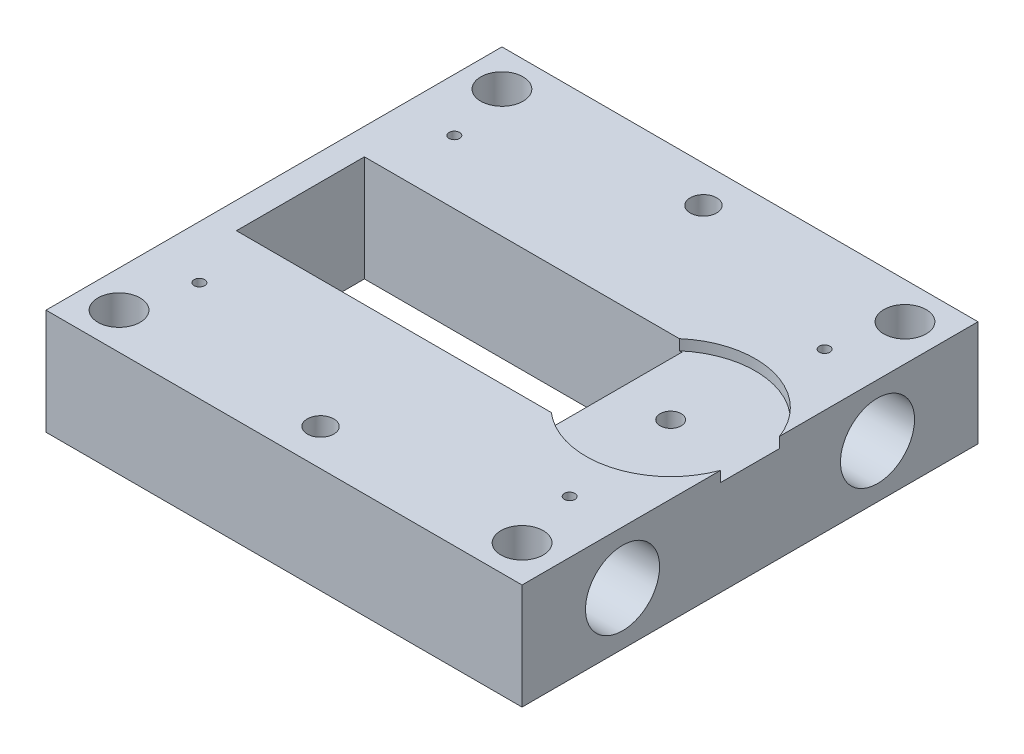
SolidWorks part; units mm, degrees
ref_plane "Front Plane" through (0, 0, 0) normal (0, 0, 1) x (1, 0, 0)
ref_plane "Top Plane" through (0, 0, 0) normal (0, 1, 0) x (1, 0, 0)
ref_plane "Right Plane" through (0, 0, 0) normal (1, 0, 0) x (0, 0, -1)
sketch "Sketch2" plane through (0, 0, 0) normal (1, 0, 0) x (0, 0, -1)
  line L0 (-24.1, 0) -> (24.1, 0) construction
  line L5 (-38.1, 0) -> (38.1, 0) construction
  line L6 (-43.1, -10) -> (43.1, -10)
  line L7 (-43.1, -10) -> (-43.1, 10)
  line L8 (-43.1, 10) -> (43.1, 10)
  line L9 (43.1, -10) -> (43.1, 10)
  line L10 (-43.1, -10) -> (43.1, 10) construction
  line L11 (-43.1, 10) -> (43.1, -10) construction
  circle A0 centre (-24.1, 0) radius 7
  circle A1 centre (24.1, 0) radius 7
  point P4 (0, 0)
  point P6 (0, 0)
  point P12 (-24.1, 7)
  point P14 (-31.1, 0)
  dimension "D1" = 14
  dimension "D2" = 3
  dimension "D3" = 76.2
  dimension "D4" = 5
  dimension "D5" = 7
extrude "Boss-Extrude1" add sketch "Sketch2" along normal mid plane 90
sketch "Sketch3" plane through (0, -10, 0) normal (0, -1, 0) x (1, 0, 0)
  line L1 (-38.1, -36.195) -> (38.1, -36.195) construction
  line L2 (-38.1, -36.195) -> (-38.1, 36.195) construction
  line L3 (-38.1, 36.195) -> (38.1, 36.195) construction
  line L4 (38.1, -36.195) -> (38.1, 36.195) construction
  line L5 (-38.1, -36.195) -> (38.1, 36.195) construction
  line L6 (-38.1, 36.195) -> (38.1, -36.195) construction
  circle A0 centre (-38.1, 36.195) radius 1.375
  circle A1 centre (38.1, 36.195) radius 1.375
  circle A2 centre (38.1, -36.195) radius 1.375
  circle A3 centre (-38.1, -36.195) radius 1.375
  point P0 (0, 0)
  dimension "D3" = 2.75
  dimension "D1" = 72.39
  dimension "D2" = 76.2
extrude "Cut-Extrude1" cut sketch "Sketch3" against normal through all
sketch "Sketch4" plane through (0, 10, 0) normal (0, 1, 0) x (1, 0, 0)
  circle A0 centre (-38.1, -36.195) radius 4
  circle A1 centre (-38.1, 36.195) radius 4
  circle A2 centre (38.1, 36.195) radius 4
  circle A3 centre (38.1, -36.195) radius 4
  dimension "D1" = 8
extrude "Cut-Extrude2" cut sketch "Sketch4" against normal offset from surface (17 mm away) 3 up to face at (-38.1, -10, -37.57)
sketch "Sketch5" plane through (0, 0, 0) normal (1, 0, 0) x (0, 0, -1)
  circle A0 centre (24.1, 0) radius 7 construction
  circle A1 centre (-24.1, 0) radius 7 construction
  circle A2 centre (24.1, 0) radius 7
  circle A3 centre (-24.1, 0) radius 7
  circle A4 centre (-24.1, 0) radius 5
  circle A5 centre (24.1, 0) radius 5
  dimension "D1" = 10
extrude "Boss-Extrude2" add sketch "Sketch5" along normal mid plane 42
sketch "Sketch6" plane through (0, 10, 0) normal (0, 1, 0) x (1, 0, 0)
  line L0 (45, 43.1) -> (45, -43.1) construction
  circle A0 centre (30, 0) radius 2
  circle A1 centre (0, -36.195) radius 2.5
  circle A2 centre (0, 36.195) radius 2.5
  circle A3 centre (-38.1, -36.195) radius 1.375 construction
  circle A4 centre (-38.1, -36.195) radius 1.375 construction
  circle A5 centre (-38.1, 36.195) radius 1.375 construction
  circle A6 centre (-38.1, 36.195) radius 1.375 construction
  dimension "D1" = 4
  dimension "D3" = 5
  dimension "D2" = 15
extrude "Cut-Extrude3" cut sketch "Sketch6" against normal through all
sketch "Sketch7" plane through (0, -10, 0) normal (0, -1, 0) x (1, 0, 0)
  circle A0 centre (30, 0) radius 5
  circle A1 centre (0, 36.195) radius 5
  circle A2 centre (0, -36.195) radius 5
  dimension "D1" = 10
extrude "Cut-Extrude4" cut sketch "Sketch7" against normal offset from surface (16 mm away) 4 up to face at (30, 10, 2)
sketch "Sketch8" plane through (0, 10, 0) normal (0, 1, 0) x (1, 0, 0)
  line L0 (45, -31.1) -> (45, -17.1) construction
  line L1 (35, 24.1) -> (-35, 24.1) construction
  line L2 (35, 24.1) -> (35, -24.1) construction
  line L3 (35, -24.1) -> (-35, -24.1) construction
  line L4 (-35, 24.1) -> (-35, -24.1) construction
  line L5 (35, 24.1) -> (-35, -24.1) construction
  line L6 (35, -24.1) -> (-35, 24.1) construction
  line L7 (45, -31.1) -> (45, -17.1) construction
  line L8 (45, 43.1) -> (45, -43.1) construction
  circle A0 centre (35, -24.1) radius 1
  circle A1 centre (-35, -24.1) radius 1
  circle A2 centre (-35, 24.1) radius 1
  circle A3 centre (35, 24.1) radius 1
  point P0 (0, 0)
  point P8 (45, -24.1)
  dimension "D2" = 2
  dimension "D1" = 10
extrude "Cut-Extrude5" cut sketch "Sketch8" against normal up to next
sketch "Sketch9" plane through (0, 10, 0) normal (0, 1, 0) x (1, 0, 0)
  line L0 (-21, -17.1) -> (-45, -17.1) construction
  line L1 (20, -12.1) -> (-40, -12.1)
  line L2 (20, -12.1) -> (20, 12.1)
  line L3 (20, 12.1) -> (-40, 12.1)
  line L4 (-40, -12.1) -> (-40, 12.1)
  line L5 (20, -12.1) -> (-40, 12.1) construction
  line L6 (20, 12.1) -> (-40, -12.1) construction
  line L7 (-45, 43.1) -> (-45, -43.1) construction
  circle A0 centre (30, 0) radius 5 construction
  circle A1 centre (30, 0) radius 2 construction
  circle A2 centre (30, 0) radius 2 construction
  point P0 (-10, 0)
  point P12 (25, 0)
  dimension "D1" = 5
  dimension "D2" = 5
  dimension "D3" = 5
extrude "Cut-Extrude6" cut sketch "Sketch9" against normal through all
sketch "Sketch10" plane through (0, 10, 0) normal (0, 1, 0) x (1, 0, 0)
  circle A0 centre (30, 0) radius 16
  dimension "D1" = 32
extrude "Cut-Extrude7" cut sketch "Sketch10" against normal blind 2
sketch "Sketch11" plane through (0, 6, 0) normal (0, -1, 0) x (1, 0, 0)
  circle A0 centre (30, 0) radius 2 construction
  circle A1 centre (30, 0) radius 5
  circle A2 centre (30, 0) radius 5
  circle A3 centre (30, 0) radius 2
  dimension "D1" = 0
extrude "Boss-Extrude3" add sketch "Sketch11" along normal offset from surface (2 mm away) 4 up to face at (28.7469, 8, 0)
